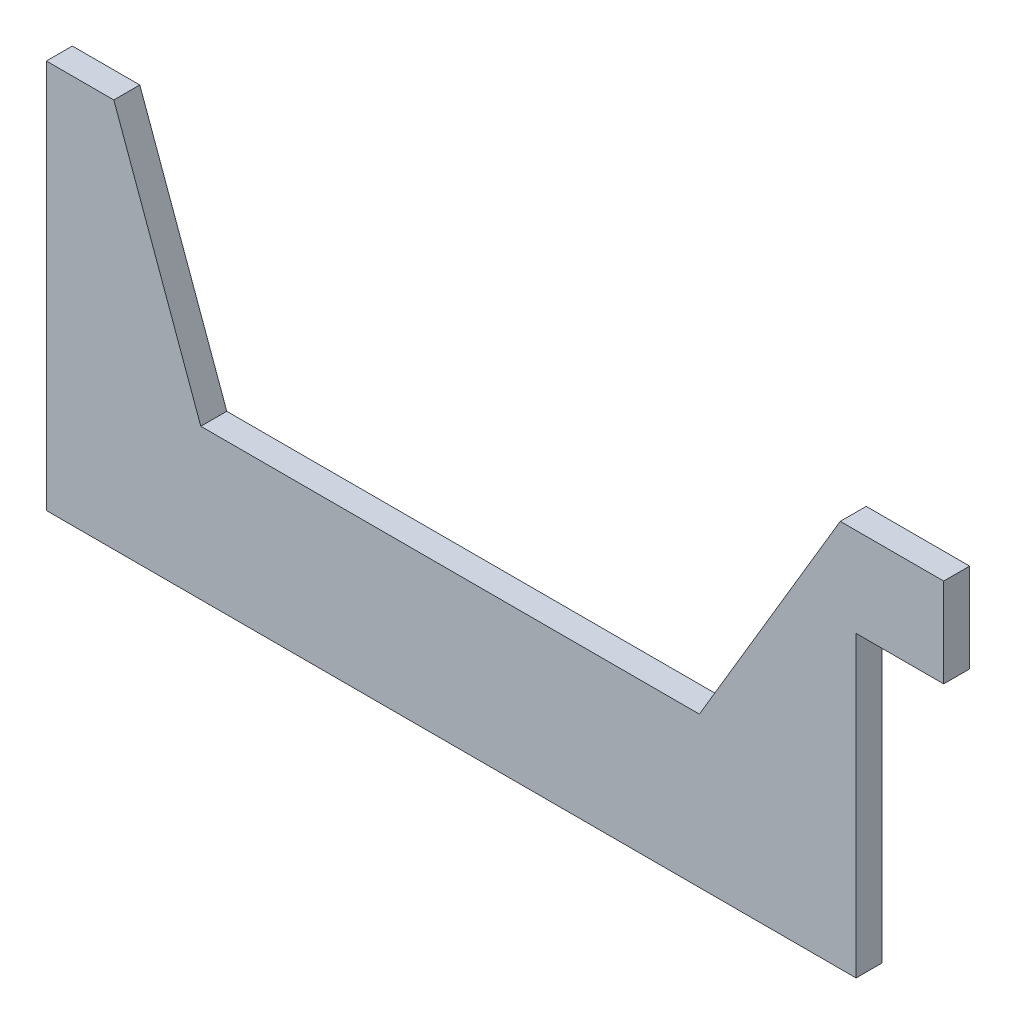
SolidWorks part; units mm, degrees
ref_plane "Front Plane" through (0, 0, 0) normal (0, 0, 1) x (1, 0, 0)
ref_plane "Top Plane" through (0, 0, 0) normal (0, 1, 0) x (1, 0, 0)
ref_plane "Right Plane" through (0, 0, 0) normal (1, 0, 0) x (0, 0, -1)
sketch "Sketch1" plane through (0, 0, 0) normal (0, 0, 1) x (1, 0, 0)
  line L2 (-60.75, -30) -> (-60.75, 30)
  line L11 (64.0497, 16) -> (77.5497, 16)
  line L18 (64.0497, -30) -> (64.0497, 16)
  line L21 (77.5497, 29.7321) -> (77.5497, 16)
  line L23 (-60.75, 30) -> (-50.3529, 30)
  line L24 (-50.3529, 30) -> (-36.9454, -6.8552)
  line L25 (-36.9454, -6.8552) -> (39.8971, -6.8552)
  line L26 (39.8971, -6.8552) -> (61.6068, 29.7321)
  line L27 (61.6068, 29.7321) -> (77.5497, 29.7321)
  line L29 (-60.75, -30) -> (64.0497, -30)
  point P13 (-60.75, 0)
  dimension "D1" = 138.3
  dimension "D2" = 13.5
  dimension "D3" = 46
  dimension "D4" = 60
extrude "Boss-Extrude1" add sketch "Sketch1" along normal mid plane 4
equation "\"wall_thick_ness\"=4"
equation "\"D1@Boss-Extrude1\"=\"wall_thick_ness\""
equation "\"back_boost\"=7"
equation "\"D1@Sketch1\"=\"back_boost\"+131.30mm"
